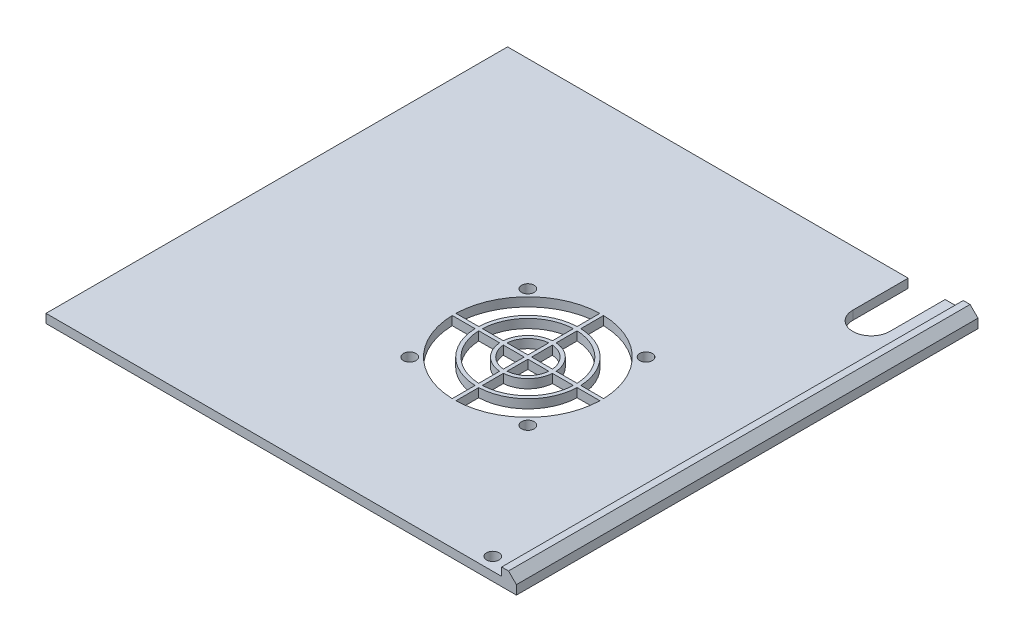
SolidWorks part; units mm, degrees
material "ABS"
ref_plane "Front Plane" through (0, 0, 0) normal (0, 0, 1) x (1, 0, 0)
ref_plane "Top Plane" through (0, 0, 0) normal (0, 1, 0) x (1, 0, 0)
ref_plane "Right Plane" through (0, 0, 0) normal (1, 0, 0) x (0, 0, -1)
ref_axis "Axis1" through (0, 0, 55) along (0, 0, -1)
sketch "Sketch1" plane through (0, 0, 0) normal (0, 1, 0) x (1, 0, 0)
  line L1 (-60.75, 62.5) -> (60.75, 62.5)
  line L2 (-60.75, 62.5) -> (-60.75, -62.5)
  line L3 (-60.75, -62.5) -> (60.75, -62.5)
  line L4 (60.75, 62.5) -> (60.75, -62.5)
  line L5 (-60.75, 62.5) -> (60.75, -62.5) construction
  line L6 (-60.75, -62.5) -> (60.75, 62.5) construction
  point P0 (0, 0)
  dimension "D1" = 121.5
  dimension "D2" = 125
extrude "Boss-Extrude1" add sketch "Sketch1" along normal blind 2.4
sketch "4040-extrusion" plane through (0, 0, 62.5) normal (0, 0, 1) x (1, 0, 0)
  line L0 (60.75, 0) -> (60.75, 9.5) construction
  line L1 (60.75, 9.5) -> (60.75, 4.3) construction
  line L2 (60.75, 4.3) -> (62.55, 2.5) construction
  line L3 (62.55, 2.5) -> (62.55, 4.71) construction
  line L4 (62.55, 4.71) -> (64.55, 4.71) construction
  line L5 (64.55, 4.71) -> (66.75, 2.5118) construction
  line L6 (66.75, 2.5118) -> (66.75, 0) construction
  dimension "D1" = 9.5
  dimension "D2" = 5.2
  dimension "D3" = 7
  dimension "D4" = 1.8
  dimension "D5" = 2
  dimension "D6" = 3.11
  dimension "D7" = 2.21
  dimension "D8" = 6
sketch "Sketch3" plane through (0, 0, 62.5) normal (0, 0, 1) x (1, 0, 0)
  line L0 (60.75, 0) -> (60.75, 2.4)
  line L1 (60.75, 2.4) -> (62.55, 2.4)
  line L2 (62.55, 2.4) -> (62.55, 4.71) construction
  line L3 (62.55, 4.71) -> (64.55, 4.71) construction
  line L4 (64.55, 4.71) -> (66.75, 2.5118) construction
  line L5 (66.75, 2.5118) -> (66.75, 0) construction
  line L6 (66.75, 0) -> (66.65, 0) construction
  line L7 (62.65, 2.4) -> (62.65, 4.61)
  line L8 (62.65, 4.61) -> (64.5086, 4.61)
  line L9 (64.5086, 4.61) -> (66.65, 2.4704)
  line L10 (66.65, 2.4704) -> (66.65, 0)
  line L11 (62.55, 2.4) -> (62.65, 2.4)
  line L12 (66.65, 0) -> (60.75, 0)
  dimension "D1" = 0.1
extrude "Boss-Extrude2" add sketch "Sketch3" against normal up to surface (125 mm away) up to face at (0, 1.2, -62.5)
sketch "Sketch4" plane through (0, 2.4, 0) normal (0, 1, 0) x (1, 0, 0)
  line L0 (-60.75, -62.5) -> (62.65, -62.5) construction
  line L1 (53.25, -62.5) -> (60.25, -62.5) construction
  line L2 (53.25, -62.5) -> (53.25, -55.5) construction
  line L3 (53.25, -55.5) -> (60.25, -55.5) construction
  line L4 (60.25, -62.5) -> (60.25, -55.5) construction
  line L5 (53.25, -62.5) -> (60.25, -55.5) construction
  line L6 (53.25, -55.5) -> (60.25, -62.5) construction
  line L7 (56.75, -59) -> (62.65, -59) construction
  line L9 (62.65, 62.5) -> (62.65, -62.5) construction
  circle A0 centre (56.75, -59) radius 1.7
  point P4 (56.75, -59)
  dimension "D2" = 3.4
  dimension "D1" = 7
  dimension "D3" = 5.9
extrude "Cut-Extrude1" cut sketch "Sketch4" against normal through all
sketch "Sketch5" plane through (0, 2.4, 0) normal (0, 1, 0) x (1, 0, 0)
  line L0 (52.75, 62.5) -> (52.75, 47.5) construction
  line L1 (62.65, 62.5) -> (-60.75, 62.5) construction
  line L2 (57.75, 62.5) -> (57.75, 47.5)
  line L3 (47.75, 62.5) -> (47.75, 47.5)
  line L4 (52.75, 55) -> (62.65, 55) construction
  line L6 (47.75, 62.5) -> (57.75, 62.5)
  line L7 (62.65, 62.5) -> (62.65, -62.5) construction
  arc A0 (57.75, 62.5) -> (47.75, 62.5) centre (52.75, 62.5) ccw
  arc A1 (47.75, 47.5) -> (57.75, 47.5) centre (52.75, 47.5) ccw
  point P4 (52.75, 55)
  line M7 (62.65, 62.5) -> (-60.75, 62.5)
  dimension "D1" = 15
  dimension "D2" = 5
  dimension "D3" = 9.9
extrude "Cut-Extrude2" cut sketch "Sketch5" against normal through all contours L3 A1 L2 M7 region at (52.75, 2.4, -53.0036)
sketch "Sketch6" plane through (0, 2.4, 0) normal (0, 1, 0) x (1, 0, 0)
  line L0 (14.75, -7.5) -> (14.75, -62.5) construction
  line L1 (-5.25, 12.5) -> (34.75, 12.5) construction
  line L2 (-5.25, 12.5) -> (-5.25, -27.5) construction
  line L3 (-5.25, -27.5) -> (34.75, -27.5) construction
  line L4 (34.75, 12.5) -> (34.75, -27.5) construction
  line L5 (-5.25, 12.5) -> (34.75, -27.5) construction
  line L6 (-5.25, -27.5) -> (34.75, 12.5) construction
  line L7 (-60.75, -62.5) -> (60.75, -62.5) construction
  line L8 (14.75, -7.5) -> (60.75, -7.5) construction
  line L9 (60.75, 62.5) -> (60.75, -62.5) construction
  line L11 (-1.25, 8.5) -> (30.75, 8.5) construction
  line L12 (-1.25, 8.5) -> (-1.25, -23.5) construction
  line L13 (-1.25, -23.5) -> (30.75, -23.5) construction
  line L14 (30.75, 8.5) -> (30.75, -23.5) construction
  line L15 (-1.25, 8.5) -> (30.75, -23.5) construction
  line L16 (-1.25, -23.5) -> (30.75, 8.5) construction
  circle A0 centre (-1.25, -23.5) radius 1.7
  circle A1 centre (30.75, -23.5) radius 1.7
  circle A2 centre (30.75, 8.5) radius 1.7
  circle A3 centre (-1.25, 8.5) radius 1.7
  circle A4 centre (14.75, -7.5) radius 20 construction
  point P0 (14.75, -7.5)
  dimension "D4" = 3.4
  dimension "D1" = 46
  dimension "D2" = 55
  dimension "D3" = 40
  dimension "D5" = 32
extrude "Cut-Extrude3" cut sketch "Sketch6" against normal through all
sketch "Sketch7" plane through (0, 2.4, 0) normal (0, 1, 0) x (1, 0, 0)
  line L0 (14.7563, -7.5) -> (14.7563, 12.4937) construction
  line L1 (14.7563, -7.5) -> (21.4208, -7.5) construction
  line L2 (21.4208, -7.5) -> (28.0854, -7.5) construction
  line L3 (28.0854, -7.5) -> (34.75, -7.5) construction
  line L4 (28.0854, -7) -> (34.75, -7)
  line L5 (21.4208, -7) -> (28.0854, -7)
  line L6 (15.2563, -7) -> (21.4208, -7)
  line L7 (15.2563, -7) -> (15.2563, 12.4937)
  line L8 (34.75, 12.5) -> (34.75, -27.5) construction
  line L9 (14.75, -7.5) -> (60.75, -7.5) construction
  arc A2 (14.7563, -0.8354) -> (21.4208, -7.5) centre (14.7563, -7.5) cw construction
  arc A3 (14.7563, 5.8292) -> (28.0854, -7.5) centre (14.7563, -7.5) cw construction
  arc A4 (14.7563, -1.3354) -> (20.9208, -7.5) centre (14.7563, -7.5) cw
  arc A5 (14.7563, 5.3292) -> (27.5854, -7.5) centre (14.7563, -7.5) cw
  arc A6 (14.7563, -0.3354) -> (21.9208, -7.5) centre (14.7563, -7.5) cw
  arc A7 (14.7563, 6.3292) -> (28.5854, -7.5) centre (14.7563, -7.5) cw
  arc A8 (15.2563, 12.4937) -> (34.75, -7) centre (14.7563, -7.5) cw
  circle A9 centre (14.75, -7.5) radius 20 construction
  arc A10 (14.7563, -1.3354) -> (20.9208, -7.5) centre (14.7563, -7.5) cw construction
  dimension "D1" = 0.5
  dimension "D2" = 0.5
  dimension "D3" = 0.5
extrude "Cut-Extrude4" cut sketch "Sketch7" against normal through all contours A4 L7 L6 | L7 A6 L5 A5 | A8 L7 A7 L4 region at (25.7341, 2.4, -3.4778) region at (21.3869, 2.4, 0.8693) region at (17.5927, 2.4, 4.6635)
pattern_circular "CirPattern1" count 4 every 90 about axis through (14.7563, 0, 7.5) along (0, 1, 0) of "Cut-Extrude4"
